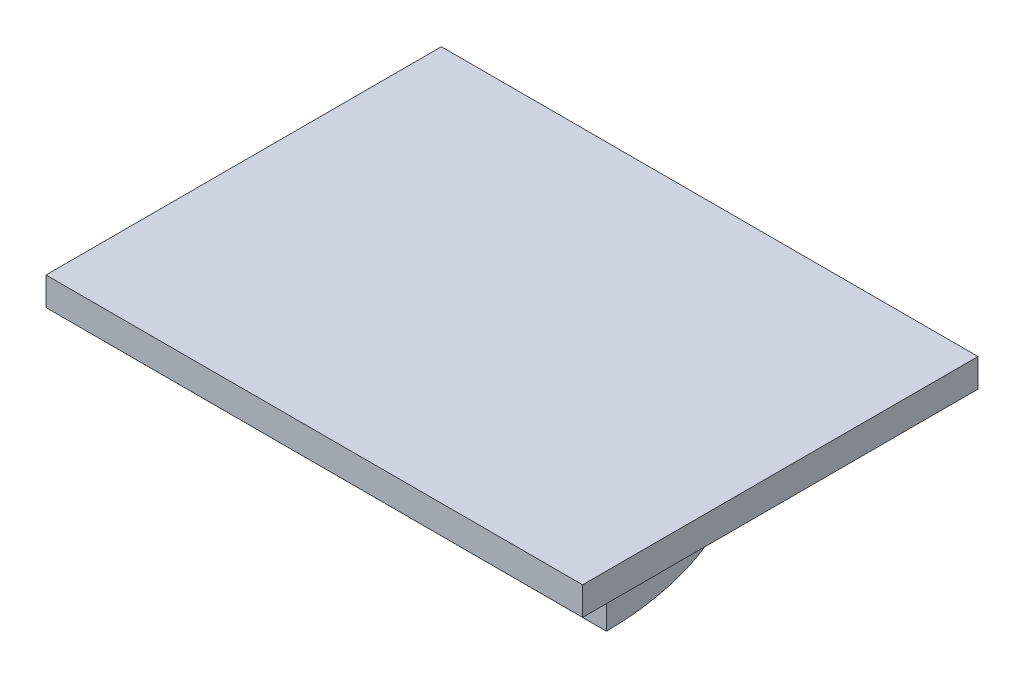
SolidWorks part; units mm, degrees
ref_plane "Front Plane" through (0, 0, 0) normal (0, 0, 1) x (1, 0, 0)
ref_plane "Top Plane" through (0, 0, 0) normal (0, 1, 0) x (1, 0, 0)
ref_plane "Right Plane" through (0, 0, 0) normal (1, 0, 0) x (0, 0, -1)
sketch "Sketch3" plane through (0, 0, 0) normal (0, 1, 0) x (1, 0, 0)
  line L1 (10.7886, 3.3538) -> (28.6886, 3.3538)
  line L2 (10.7886, 3.3538) -> (10.7886, -8.5462)
  line L3 (10.7886, -8.5462) -> (28.6886, -8.5462)
  line L4 (28.6886, 3.3538) -> (28.6886, -8.5462)
  dimension "D1" = 11.9
  dimension "D2" = 17.9
extrude "Boss-Extrude3" add sketch "Sketch3" along normal blind 1.4 separate body
fillet "Fillet2" radius 12 2 edges at (10.7886, 0.7, -3.3538) (28.6886, 0.7, -3.3538)
sketch "Sketch4" plane through (0, 1.4, 0) normal (0, 1, 0) x (1, 0, 0)
  line L0 (19.7386, 2.9598) -> (19.7386, -8.5462) construction
  line L1 (10.7886, -8.5462) -> (28.6886, -8.5462) construction
  line L3 (10.2386, 4.0558) -> (29.2386, 4.0558)
  line L4 (10.2386, 4.0558) -> (10.2386, -9.9442)
  line L5 (10.2386, -9.9442) -> (29.2386, -9.9442)
  line L6 (29.2386, 4.0558) -> (29.2386, -9.9442)
  line L7 (10.2386, 4.0558) -> (29.2386, -9.9442) construction
  line L8 (10.2386, -9.9442) -> (29.2386, 4.0558) construction
  point P5 (19.7386, -2.9442)
  dimension "D1" = 14
  dimension "D2" = 19
extrude "Boss-Extrude4" add sketch "Sketch4" along normal blind 1
